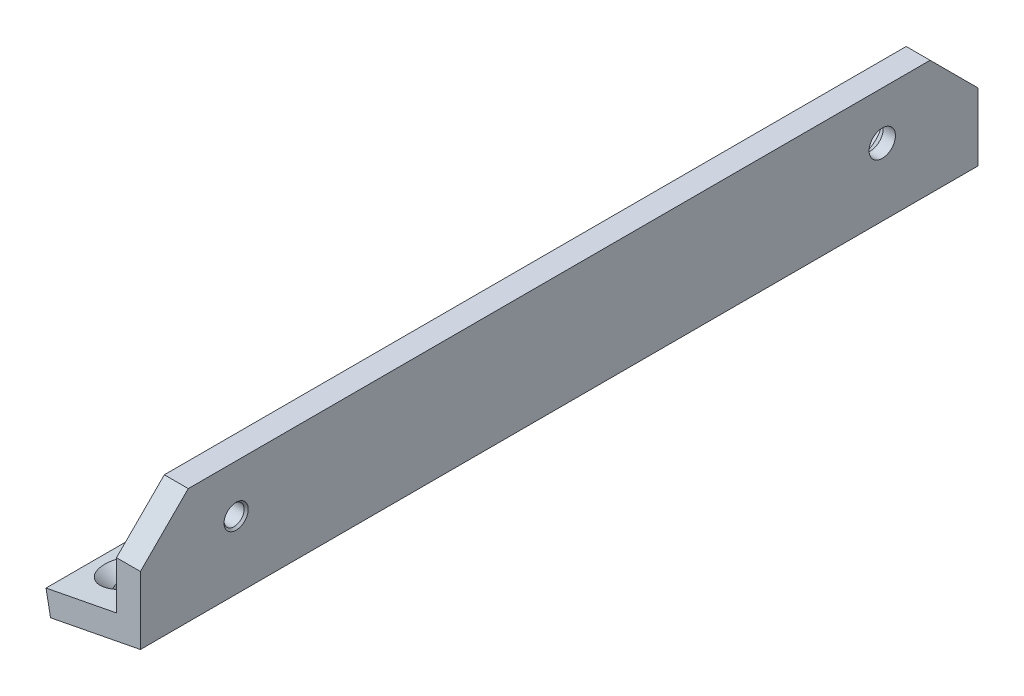
SolidWorks part; units mm, degrees
material "6063-T6"
ref_plane "Plan de face" through (0, 0, 0) normal (0, 0, 1) x (1, 0, 0)
ref_plane "Plan de dessus" through (0, 0, 0) normal (0, 1, 0) x (1, 0, 0)
ref_plane "Plan de droite" through (0, 0, 0) normal (1, 0, 0) x (0, 0, -1)
sketch "Esquisse1" plane through (0, 0, 0) normal (0, 0, 1) x (1, 0, 0)
  line L0 (-10, 24.1238) -> (-10, 0)
  line L1 (-10, 120) -> (-10, 0) construction
  line L2 (-10, 24.1238) -> (-15, 24.1238)
  line L3 (-15, 24.1238) -> (-15, 4.1238)
  line L4 (-29.7259, 1.2691) -> (-28.7743, -3.6395)
  line L5 (-15, 4.1238) -> (-10, 0) construction
  line L6 (-15, 4.1238) -> (-29.7259, 1.2691)
  line L7 (-29.2501, -1.1852) -> (-12.5, 2.0619) construction
  line L8 (-12.5, 2.0619) -> (-12.5, 24.1238) construction
  line L9 (-10, 0) -> (-28.7743, -3.6395)
  circle A2 centre (-5, -76.0358) radius 76.2 construction
  point P5 (-28.7324, -3.6257)
  point P15 (-22.4082, -1.8509)
  dimension "D1" = 5
  dimension "D2" = 5
  dimension "D3" = 20
  dimension "D5" = 15
  dimension "D6" = 90
extrude "Boss.-Extru.1" add sketch "Esquisse1" along normal blind 175 contours L6 L4 L9 L0 L2 L3
chamfer "Chanfrein1" distance 10 angle 45 2 edges at (-12.5, 24.1238, 175) (-12.5, 24.1238, 0)
hole_wizard "Fraisage pour vis à tête fraisée M51" positions "Esquisse2" profile "Esquisse3" countersink size "M5" standard "DIN"
sketch "Esquisse2" plane through (-15, 0, 0) normal (-1, 0, 0) x (0, 0, 1)
  line L0 (20, 24.1238) -> (20, 4.1238) construction
  line L1 (165, 24.1238) -> (10, 24.1238) construction
  line L2 (175, 4.1238) -> (0, 4.1238) construction
  line L3 (0, 14.1238) -> (0, 4.1238) construction
  point P9 (20, 14.1238)
  dimension "D1" = 20
sketch "Esquisse3" plane through (-15, 14.1238, 20) normal (0, 1, 0) x (0, 0, 1)
  line L0 (0, 0) -> (0, 26.6524)
  line L1 (0, 26.6524) -> (2.75, 25)
  line L2 (2.75, 25) -> (2.75, 2.45)
  line L3 (2.75, 2.45) -> (5.2, 0)
  line L5 (5.2, 0) -> (0, 0)
  line L6 (-2.75, 2.45) -> (-5.2, 0) construction
  line L10 (0, 26.6524) -> (-2.75, 25) construction
  line L11 (0, -6.35) -> (0, 107.95) construction
  dimension "Diamètre du perçage" = 5.5
  dimension "Profondeur du perçage" = 25
  dimension "Diamètre du fraisage entrant" = 10.4
  dimension "Angle du fraisage entrant" = 90
  dimension "Angle de pointe" = 118
hole_wizard "Trou taraudé M51" positions "Esquisse4" profile "Esquisse6" tap size "M5" standard "DIN" end condition through all
sketch "Esquisse4" plane through (-10, 0, 0) normal (1, 0, 0) x (0, 0, -1)
  point P0 (-155, 14.1238)
sketch "Esquisse6" plane through (-10, 14.1238, 155) normal (0, 1, 0) x (0, 0, -1)
  line L0 (0, 0) -> (0, 19.7259)
  line L1 (0, 19.7259) -> (2.1, 19.7259)
  line L2 (2.1, 19.7259) -> (2.1, 0.425)
  line L3 (2.1, 0.425) -> (2.525, 0)
  line L5 (2.525, 0) -> (0, 0)
  line L6 (-2.1, 0.425) -> (-2.525, 0) construction
  line L11 (0, -6.35) -> (0, 107.95) construction
  dimension "Diamètre du trou pour taraudage jusqu'au prochain" = 4.2
  dimension "Profondeur du trou pour taraudage jusqu'au prochain" = 19.7259
  dimension "Diamètre du fraisage entrant" = 5.05
  dimension "Angle du fraisage entrant" = 90
cosmetic thread "Filetage de perçage1" parameters "D2"=5
hole_wizard "Fraisage pour vis à tête fraisée M52" positions "Esquisse7" profile "Esquisse8" countersink size "M5" standard "DIN" end condition through all
sketch "Esquisse7" plane through (-1.3137, 6.777, 0) normal (-0.1903, 0.9817, 0) x (0.9817, 0.1903, 0)
  line L0 (-21.441, -175) -> (-21.441, -165) construction
  line L1 (-13.941, -175) -> (-28.941, -175) construction
  line L2 (-21.441, -165) -> (-21.441, -87.5) construction
  line L3 (-21.441, -87.5) -> (-21.441, -10) construction
  line L4 (-21.441, -10) -> (-21.441, 0) construction
  line L5 (-13.941, 0) -> (-28.941, 0) construction
  point P0 (-21.441, -87.5)
  point P2 (-21.441, -165)
  point P4 (-21.441, -10)
  point P19 (-21.441, -159.7608)
  point P21 (0, 0)
  dimension "D1" = 10
sketch "Esquisse8" plane through (-22.3629, 2.6965, 87.5) normal (0, 0, 1) x (-0.9817, -0.1903, 0)
  line L0 (0, 0) -> (0, 8.573)
  line L1 (0, 8.573) -> (2.75, 8.573)
  line L2 (2.75, 8.573) -> (2.75, 2.45)
  line L3 (2.75, 2.45) -> (5.2, 0)
  line L5 (5.2, 0) -> (0, 0)
  line L6 (-2.75, 2.45) -> (-5.2, 0) construction
  line L11 (0, -6.35) -> (0, 107.95) construction
  dimension "Diamètre du perçage jusqu'au prochain" = 5.5
  dimension "Profondeur du perçage jusqu'au prochain" = 8.573
  dimension "Diamètre du fraisage entrant" = 10.4
  dimension "Angle du fraisage entrant" = 90
